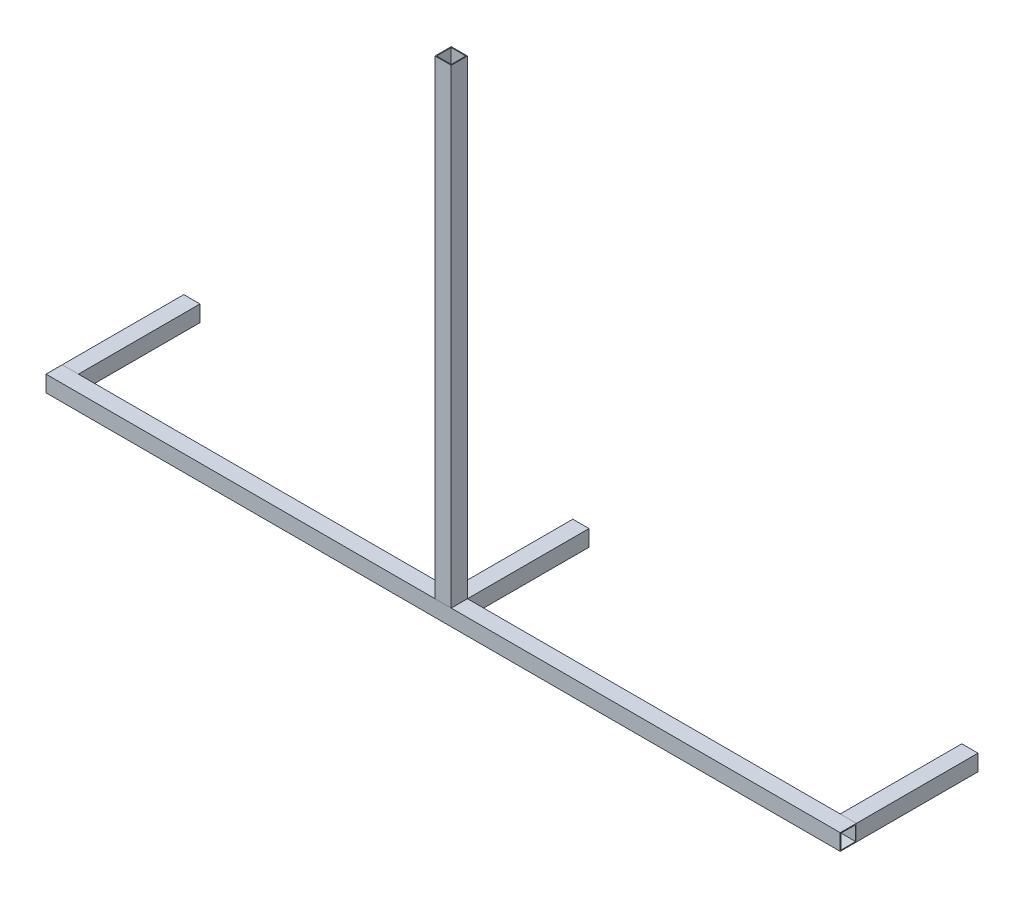
SolidWorks part; units mm, degrees
ref_plane "Alzado" through (0, 0, 0) normal (0, 0, 1) x (1, 0, 0)
ref_plane "Planta" through (0, 0, 0) normal (0, 1, 0) x (1, 0, 0)
ref_plane "Vista lateral" through (0, 0, 0) normal (1, 0, 0) x (0, 0, -1)
sketch "Croquis1" plane through (0, 0, 0) normal (1, 0, 0) x (0, 0, -1)
  line L1 (10, -10) -> (-10, -10)
  line L2 (10, -10) -> (10, 10)
  line L3 (10, 10) -> (-10, 10)
  line L4 (-10, -10) -> (-10, 10)
  line L5 (10, -10) -> (-10, 10) construction
  line L6 (10, 10) -> (-10, -10) construction
  point P0 (0, 0)
  dimension "D1" = 20
extrude "Extruir-Lámina1" add sketch "Croquis1" along normal mid plane 980 thin thin type one direction reverse wall 1
sketch "Croquis2" plane through (0, 0, -10) normal (0, 0, -1) x (-1, 0, 0)
  line L1 (10, -10) -> (-10, -10)
  line L2 (10, -10) -> (10, 10)
  line L3 (10, 10) -> (-10, 10)
  line L4 (-10, -10) -> (-10, 10)
  line L5 (10, -10) -> (-10, 10) construction
  line L6 (10, 10) -> (-10, -10) construction
  line L7 (-490, -10) -> (-490, 10) construction
  line L8 (-490, 10) -> (490, 10) construction
  circle A0 centre (0, 0) radius 14.1421 construction
  point P0 (0, 0)
  dimension "D1" = 20
extrude "Extruir-Lámina3" add sketch "Croquis2" along normal blind 150 separate body thin thin type one direction reverse wall 1
sketch "Croquis3" plane through (0, 0, -10) normal (0, 0, -1) x (-1, 0, 0)
  line L0 (-490, -10) -> (490, -10) construction
  line L1 (-490, 10) -> (-470, 10)
  line L2 (-490, 10) -> (-490, -10)
  line L3 (-490, -10) -> (-470, -10)
  line L4 (-470, 10) -> (-470, -10)
  line L5 (470, 10) -> (490, -10) construction
  line L6 (490, 10) -> (470, 10)
  line L7 (490, 10) -> (490, -10)
  line L8 (490, -10) -> (470, -10)
  line L9 (470, 10) -> (470, -10)
  line L10 (-490, 10) -> (-470, -10) construction
  line L11 (-490, 10) -> (490, 10) construction
  circle A0 centre (480, 0) radius 27.5772 construction
  circle A1 centre (-480, 0) radius 14.1421 construction
extrude "Extruir-Lámina5" add sketch "Croquis3" along normal blind 150 separate body thin thin type one direction reverse wall 1
sketch "Croquis4" plane through (0, 10, 0) normal (0, 1, 0) x (1, 0, 0)
  line L1 (10, -10) -> (-10, -10)
  line L2 (10, -10) -> (10, 10)
  line L3 (10, 10) -> (-10, 10)
  line L4 (-10, -10) -> (-10, 10)
  line L5 (10, -10) -> (-10, 10) construction
  line L6 (10, 10) -> (-10, -10) construction
  circle A0 centre (0, 0) radius 14.1421 construction
  point P0 (0, 0)
extrude "Extruir-Lámina6" add sketch "Croquis4" along normal blind 580 separate body thin thin type one direction reverse wall 1
